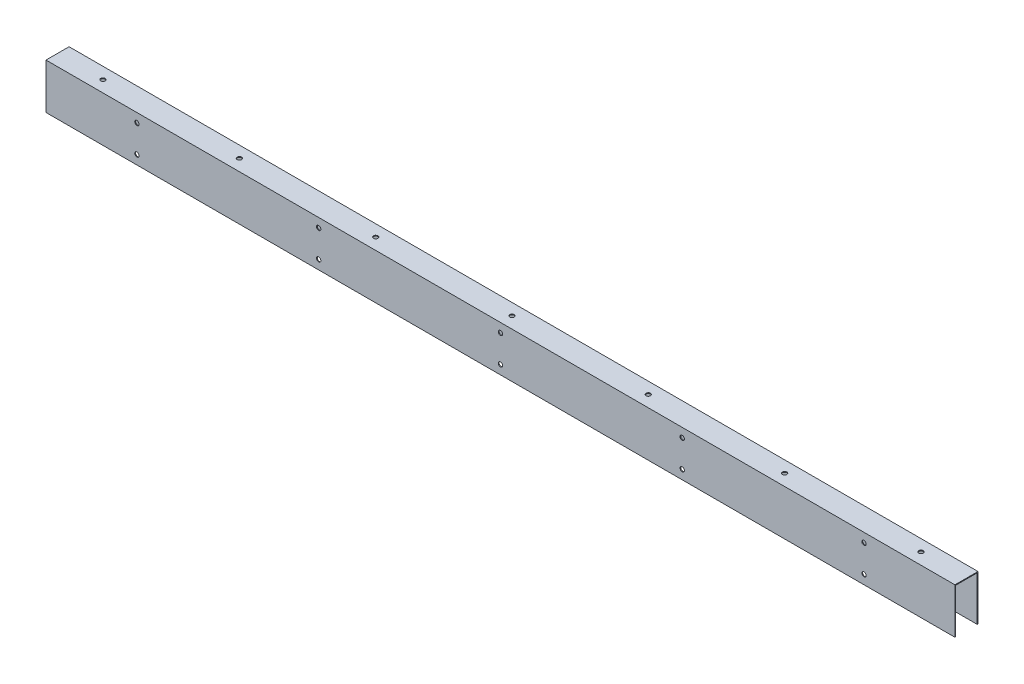
SolidWorks part; units mm, degrees
ref_plane "Front Plane" through (0, 0, 0) normal (0, 0, 1) x (1, 0, 0)
ref_plane "Top Plane" through (0, 0, 0) normal (0, 1, 0) x (1, 0, 0)
ref_plane "Right Plane" through (0, 0, 0) normal (1, 0, 0) x (0, 0, -1)
sketch "Sketch2" plane through (0, 0, 0) normal (0, 1, 0) x (1, 0, 0)
  line L1 (-500, 12.7) -> (500, 12.7)
  line L2 (-500, 12.7) -> (-500, -12.7)
  line L3 (-500, -12.7) -> (500, -12.7)
  line L4 (500, 12.7) -> (500, -12.7)
  line L5 (-500, 12.7) -> (500, -12.7) construction
  line L6 (-500, -12.7) -> (500, 12.7) construction
  point P0 (0, 0)
  dimension "D1" = 1000
  dimension "D2" = 25.4
extrude "Boss-Extrude1" add sketch "Sketch2" along normal blind 25 and the other way blind 25
sketch "Sketch4" plane through (0, 0, 0) normal (1, 0, 0) x (0, 0, -1)
  line L0 (-12.7, 25) -> (12.7, 25) construction
  line L1 (-11.84, 24.14) -> (11.84, 24.14)
  line L2 (-11.84, 24.14) -> (-11.84, -25.5732)
  line L3 (-11.84, -25.5732) -> (11.84, -25.5732)
  line L4 (11.84, 24.14) -> (11.84, -25.5732)
  line L5 (12.7, -25) -> (12.7, 25) construction
  line L6 (-12.7, -25) -> (-12.7, 25) construction
  dimension "D1" = 0.86
  dimension "D2" = 0.86
  dimension "D3" = 0.86
extrude "Cut-Extrude1" cut sketch "Sketch4" against normal blind 762 and the other way blind 762
sketch "Sketch5" plane through (0, 0, 0) normal (0, 1, 0) x (1, 0, 0)
  line L0 (-500, 0) -> (500, 0) construction
  line L1 (-500, 12.7) -> (-500, -12.7) construction
  line L2 (500, -12.7) -> (500, 12.7) construction
  circle A0 centre (0, 0) radius 2.45
  circle A1 centre (150, 0) radius 2.45
  circle A2 centre (300, 0) radius 2.45
  circle A3 centre (450, 0) radius 2.45
  circle A4 centre (-150, 0) radius 2.45
  circle A5 centre (-300, 0) radius 2.45
  circle A6 centre (-450, 0) radius 2.45
  dimension "D1" = 4
  dimension "D3" = 4.9
  dimension "D2" = 150
  dimension "D5" = 150
  dimension "D4" = 4
extrude "Cut-Extrude2" cut sketch "Sketch5" along normal blind 39.05
sketch "Sketch6" plane through (0, 0, 0) normal (0, 0, 1) x (1, 0, 0)
  line L0 (-543.3004, 15) -> (543.3004, 15) construction
  line L1 (543.3004, 15) -> (543.3004, -15) construction
  line L2 (543.3004, -15) -> (-543.3004, -15) construction
  line L3 (-543.3004, -15) -> (-543.3004, 15) construction
  line L4 (0, 15) -> (0, -15) construction
  circle A0 centre (0, 15) radius 2.4
  circle A1 centre (0, -15) radius 2.4
  circle A2 centre (200, 15) radius 2.4
  circle A3 centre (200, -15) radius 2.4
  circle A4 centre (400, 15) radius 2.4
  circle A5 centre (400, -15) radius 2.4
  circle A6 centre (600, 15) radius 2.4
  circle A7 centre (600, -15) radius 2.4
  circle A8 centre (-200, 15) radius 2.4
  circle A9 centre (-200, -15) radius 2.4
  circle A10 centre (-400, 15) radius 2.4
  circle A11 centre (-400, -15) radius 2.4
  circle A12 centre (-600, 15) radius 2.4
  circle A13 centre (-600, -15) radius 2.4
  dimension "D2" = 4
  dimension "D6" = 4.8
  dimension "D1" = 30
  dimension "D4" = 200
  dimension "D5" = 200
  dimension "D3" = 4
extrude "Cut-Extrude3" cut sketch "Sketch6" against normal blind 39.05 and the other way blind 39.05 contours A12 | A13 | A10 | A11 | A8 | A9 | A0 | A1 | A2 | A3 | A4 | A5 | A6 | A7
